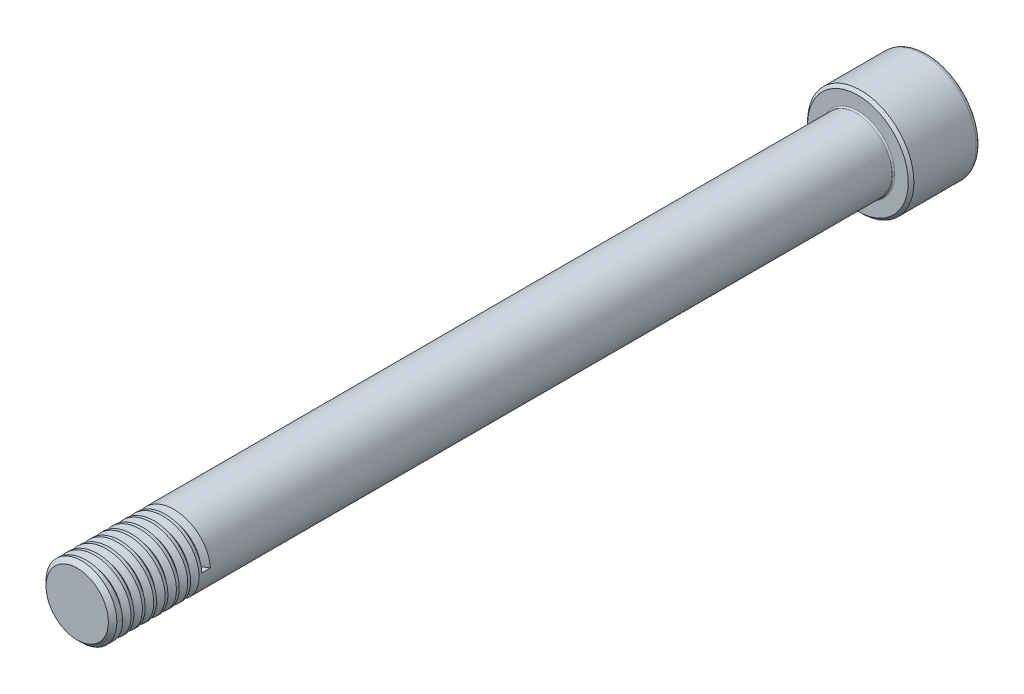
SolidWorks part; units mm, degrees
material "2014 Alloy"
ref_plane "Front Plane" through (0, 0, 0) normal (0, 0, 1) x (1, 0, 0)
ref_plane "Top Plane" through (0, 0, 0) normal (0, 1, 0) x (1, 0, 0)
ref_plane "Right Plane" through (0, 0, 0) normal (1, 0, 0) x (0, 0, -1)
sketch "Sketch1" plane through (0, 0, 0) normal (0, 0, 1) x (1, 0, 0)
  circle A0 centre (0, 0) radius 3.75
  dimension "D1" = 7.5
extrude "Boss-Extrude1" add sketch "Sketch1" along normal blind 4.9
sketch "Sketch2" plane through (0, 0, 0) normal (0, 0, -1) x (-1, 0, 0)
  line L7 (1.8543, 0) -> (2.6304, 0) construction
  arc A1 (-2, 1.1547) -> (0, 2.3094) centre (-3.2519, 5.6325) ccw
  arc A2 (2, 1.1547) -> (0, 2.3094) centre (3.2519, 5.6325) cw
  arc A3 (2, -1.1547) -> (0, -2.3094) centre (3.2519, -5.6325) ccw
  arc A4 (-2, -1.1547) -> (0, -2.3094) centre (-3.2519, -5.6325) cw
  arc A5 (-2, 1.1547) -> (-2, -1.1547) centre (-6.5038, 0) cw
  arc A6 (2, 1.1547) -> (2, -1.1547) centre (6.5038, 0) ccw
extrude "Cut-Extrude1" cut sketch "Sketch2" against normal blind 3.75
fillet "Fillet1" radius 0.3 1 edges at (3.75, 0, 0)
chamfer "Chamfer2" distance 0.3 angle 45 6 edges at (-0.9272, -1.6059, 3.75) (0.9272, -1.6059, 3.75) (1.8543, 0, 3.75) (0.9272, 1.6059, 3.75) (-0.9272, 1.6059, 3.75) (-1.8543, 0, 3.75)
fillet "Fillet2" radius 0.1 6 edges at (0.9272, 1.6059, 0) (1.8543, 0, 0) (0.9272, -1.6059, 0) (-0.9272, -1.6059, 0) (-1.8543, 0, 0) (-0.9272, 1.6059, 0)
chamfer "Chamfer4" distance 0.2 angle 45 1 edges at (3.75, 0, 4.9)
sketch "Sketch4" plane through (0, 0, 4.9) normal (0, 0, 1) x (1, 0, 0)
  circle A0 centre (0, 0) radius 2.5
  dimension "D1" = 5
extrude "Boss-Extrude2" add sketch "Sketch4" along normal blind 55.1
chamfer "Chamfer5" distance 0.3 angle 45 1 edges at (2.5, 0, 60)
thread "Thread1" pitch 0.8 method cut profile "Thread Profile1" start angle 0, offset 0, length 6, pitch 0.8, diameter 5
ref_plane "Plane1" through (-2.5, 0, 59.7) normal (0, -1, 0) x (-1, 0, 0)
sketch "Thread Profile1" plane through (-2.5, 0, 59.7) normal (0, -1, 0) x (-1, 0, 0)
  line L0 (0, 0) -> (0, 0.8) construction
  line L1 (0, 0.6) -> (-0.433, 0.35)
  line L2 (-0.433, 0.35) -> (-0.433, 0.25)
  line L3 (-0.433, 0.25) -> (0, 0)
  line L4 (-0.433, 0.3) -> (0, 0.3) construction
  line L11 (0, 0.6) -> (0, 0)
  point P6 (0, 0)
  dimension "Pitch" = 0.8
  dimension "Profile_Angle" = 60
  dimension "Profile_Land" = 0.1
  dimension "Profile_Height" = 0.433
fillet "Fillet3" radius 0.1 1 edges at (2.5, 0, 4.9)
